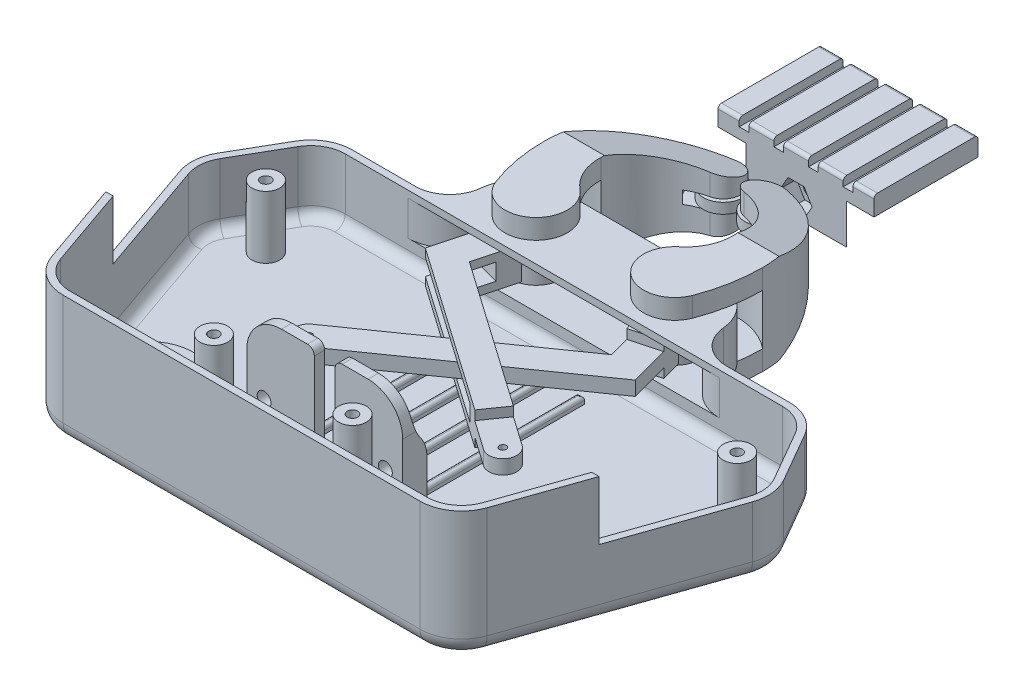
SolidWorks part; units mm, degrees
ref_plane "Front Plane" through (0, 0, 0) normal (0, 0, 1) x (1, 0, 0)
ref_plane "Top Plane" through (0, 0, 0) normal (0, 1, 0) x (1, 0, 0)
ref_plane "Right Plane" through (0, 0, 0) normal (1, 0, 0) x (0, 0, -1)
sketch "Sketch1" plane through (0, 0, 0) normal (0, 1, 0) x (1, 0, 0)
  line L0 (-70, -55) -> (-35, -55)
  line L1 (70, -55) -> (84.4338, -80)
  line L2 (84.4338, -80) -> (60, -150)
  line L3 (60, -150) -> (-60, -150)
  line L4 (-60, -150) -> (-84.4338, -80)
  line L5 (-84.4338, -80) -> (-70, -55)
  line L6 (-35, -55) -> (-35, -35)
  line L7 (-35, -35) -> (35, -35)
  line L8 (35, -35) -> (35, -55)
  line L9 (0, -55) -> (0, -122.8119) construction
  line L10 (35, -55) -> (70, -55)
  point P15 (0, -150)
  dimension "D1" = 25
  dimension "D2" = 140
  dimension "D3" = 70
  dimension "D4" = 120
  dimension "D5" = 70
  dimension "D6" = 55
  dimension "D7" = 120
  dimension "D8" = 20
  dimension "D9" = 70
  dimension "D10" = 35
extrude "Boss-Extrude1" add sketch "Sketch1" along normal blind 2
sketch "Sketch2" plane through (0, 2, 0) normal (0, 1, 0) x (1, 0, 0)
  line L0 (84.4338, -80) -> (70, -55) construction
  line L1 (60, -150) -> (84.4338, -80) construction
  line L2 (-60, -150) -> (60, -150) construction
  line L3 (-84.4338, -80) -> (-60, -150) construction
  line L4 (-70, -55) -> (-84.4338, -80) construction
  line L6 (84.4338, -80) -> (70, -55)
  line L7 (60, -150) -> (84.4338, -80)
  line L8 (-60, -150) -> (60, -150)
  line L9 (-84.4338, -80) -> (-60, -150)
  line L10 (-70, -55) -> (-84.4338, -80)
  line L11 (70, -55) -> (35, -55)
  line L12 (68.8453, -57) -> (33, -57)
  line L13 (-68.8453, -57) -> (-82.2434, -80.2062)
  line L14 (-82.2434, -80.2062) -> (-58.5798, -148)
  line L15 (-58.5798, -148) -> (58.5798, -148)
  line L16 (58.5798, -148) -> (82.2434, -80.2062)
  line L17 (82.2434, -80.2062) -> (68.8453, -57)
  line L18 (-35, -55) -> (-35, -35)
  line L19 (-35, -35) -> (35, -35)
  line L20 (35, -35) -> (35, -55)
  line L21 (-35, -55) -> (-70, -55)
  line L22 (-33, -57) -> (-33, -37)
  line L23 (70, -55) -> (-70, -55) construction
  line L24 (-33, -37) -> (33, -37)
  line L25 (33, -37) -> (33, -57)
  line L26 (-33, -57) -> (-68.8453, -57)
  line L28 (68.8453, -57) -> (-68.8453, -57) construction
  dimension "D1" = 2
  dimension "D2" = 2
  dimension "D3" = 2
  dimension "D4" = 2
extrude "Boss-Extrude2" add sketch "Sketch2" along normal blind 35
sketch "Sketch20" plane through (0, 0, 0) normal (0, -1, 0) x (1, 0, 0)
  line L0 (70, 55) -> (35, 55) construction
  line L1 (-35, 35) -> (35, 35)
  line L2 (-35, 35) -> (-35, 55)
  line L3 (-35, 55) -> (35, 55)
  line L4 (35, 35) -> (35, 55)
  line L5 (35, 55) -> (35, 35) construction
  line L6 (35, 35) -> (-35, 35) construction
  line L7 (-35, 35) -> (-35, 55) construction
extrude "Cut-Extrude7" cut sketch "Sketch20" against normal blind 8
sketch "Sketch21" plane through (0, 8, 0) normal (0, -1, 0) x (1, 0, 0)
  line L1 (-35, 35) -> (35, 35)
  line L2 (-35, 35) -> (-35, 55)
  line L3 (-35, 55) -> (35, 55)
  line L4 (35, 35) -> (35, 55)
extrude "Boss-Extrude12" add sketch "Sketch21" along normal blind 2
sketch "Sketch22" plane through (0, 0, 55) normal (0, 0, 1) x (1, 0, 0)
  line L1 (-33, 2) -> (33, 2)
  line L2 (-33, 2) -> (-33, 8)
  line L3 (-33, 8) -> (33, 8)
  line L4 (33, 2) -> (33, 8)
extrude "Boss-Extrude13" add sketch "Sketch22" along normal blind 2
sketch "Sketch23" plane through (0, 37, 0) normal (0, 1, 0) x (1, 0, 0)
  line L0 (35, -35) -> (-35, -35) construction
  line L1 (-35, -57) -> (35, -57)
  line L2 (-35, -57) -> (-35, -35)
  line L3 (-35, -35) -> (35, -35)
  line L4 (35, -57) -> (35, -35)
  line L5 (-35, -35) -> (-35, -55) construction
  line L6 (35, -55) -> (35, -35) construction
  line L7 (33, -57) -> (-33, -57) construction
extrude "Cut-Extrude8" cut sketch "Sketch23" against normal offset from surface (19 mm away) 12 up to face at (0, 6, 45)
sketch "Sketch24" plane through (0, 18, 0) normal (0, 1, 0) x (1, 0, 0)
  line L1 (-35, -35) -> (35, -35)
  line L2 (-35, -35) -> (-35, -57)
  line L3 (-35, -57) -> (35, -57)
  line L4 (35, -35) -> (35, -57)
  line L5 (-35, -35) -> (35, -35) construction
  line L6 (-35, -55) -> (-35, -35) construction
  line L8 (35, -35) -> (35, -55) construction
  line L9 (-35, -57) -> (-68.8453, -57) construction
extrude "Boss-Extrude16" add sketch "Sketch24" along normal blind 2
sketch "Sketch26" plane through (0, 0, 0) normal (0, -1, 0) x (1, 0, 0)
  line L0 (0, 35) -> (0, 168.1743) construction
  line L1 (-35, 35) -> (35, 35) construction
  circle A0 centre (20, 45) radius 7.5
  circle A1 centre (-20, 45) radius 7.5
  dimension "D1" = 15
  dimension "D2" = 10
  dimension "D3" = 20
extrude "Cut-Extrude9" cut sketch "Sketch26" against normal through all
sketch "Sketch27" plane through (0, 8, 0) normal (0, 1, 0) x (1, 0, 0)
  line L0 (-29.5, -45) -> (-27.5, -45)
  line L1 (-10.5, -45) -> (-12.5, -45)
  line L2 (0, -35) -> (0, -72.4721) construction
  line L3 (35, -35) -> (-35, -35) construction
  line L4 (29.5, -45) -> (27.5, -45)
  line L5 (10.5, -45) -> (12.5, -45)
  arc A0 (-27.5, -45) -> (-12.5, -45) centre (-20, -45) cw
  circle A1 centre (-20, -45) radius 7.5 construction
  arc A2 (-10.5, -45) -> (-29.5, -45) centre (-20, -45) ccw
  arc A3 (27.5, -45) -> (12.5, -45) centre (20, -45) ccw
  arc A4 (10.5, -45) -> (29.5, -45) centre (20, -45) cw
  dimension "D1" = 9.5
extrude "Boss-Extrude18" add sketch "Sketch27" along normal up to surface (10 mm away) up to face at (20, 18, 52.5)
sketch "Sketch25" plane through (0, 20, 0) normal (0, 1, 0) x (1, 0, 0)
  line L0 (35, -57) -> (35, -55) construction
  line L1 (-35, -57) -> (35, -57)
  line L2 (-35, -57) -> (-35, -55)
  line L3 (-35, -55) -> (35, -55)
  line L4 (35, -57) -> (35, -55)
  line L5 (-35, -57) -> (35, -57) construction
  line L6 (-35, -55) -> (-35, -57) construction
  line L7 (-35, -55) -> (-70, -55) construction
extrude "Boss-Extrude17" add sketch "Sketch25" along normal up to surface (17 mm away) up to face at (0, 37, 85.2758)
fillet "Fillet8" radius 10 2 edges at (-33, 13, 37) (33, 13, 37)
fillet "Fillet9" radius 12 2 edges at (35, 13, 35) (-35, 13, 35)
sketch "Sketch32" plane through (0, 6, 0) normal (0, -1, 0) x (1, 0, 0)
  circle A0 centre (-20, 45) radius 7.35
  circle A1 centre (-20, 45) radius 7.5 construction
  dimension "D1" = 14.7
extrude "Boss-Extrude22" add sketch "Sketch32" against normal offset from surface (14.6 mm away) 0.3 from offset 0.3 separate body up to face at (0, 20, 44.8382) offset beyond the face yes
ref_plane "Plane6" through (0, 13, 0) normal (0, -1, 0) x (-1, 0, 0)
sketch "Sketch34" plane through (0, 13, 0) normal (0, -1, 0) x (-1, 0, 0)
  line L0 (0, -55) -> (0, -6.1056) construction
  line L1 (-35, -55) -> (35, -55) construction
  circle A0 centre (6, -5) radius 6
  circle A1 centre (20, -45) radius 7.5 construction
  circle A2 centre (20, -45) radius 7.5 construction
  circle A3 centre (6, -5) radius 2.8
  dimension "D1" = 12
  dimension "D3" = 5.6
  dimension "D2" = 40
extrude "Boss-Extrude23" add sketch "Sketch34" along normal mid plane 3 separate body
sketch "Sketch36" plane through (0, 13, 0) normal (0, -1, 0) x (-1, 0, 0)
  circle A0 centre (6, -5) radius 2.5
  dimension "D1" = 5
extrude "Boss-Extrude24" add sketch "Sketch36" along normal mid plane 3.6 separate body
sketch "Sketch37" plane through (0, 11.2, 0) normal (0, -1, 0) x (1, 0, 0)
  line L0 (-1.0405, 27.7489) -> (-20, 45) construction
  line L1 (-6, 5) -> (-1.0405, 27.7489) construction
  line L2 (0.4875, 31.2396) -> (-20, 45) construction
  line L3 (0.4875, 31.2396) -> (-6, 5) construction
  arc A0 (-4.935, 9.8853) -> (-7.2001, 0.1462) centre (-6, 5) cw
  circle A1 centre (-20, 45) radius 7.35 construction
  arc A2 (-14.5636, 40.0535) -> (-26.1015, 49.0981) centre (-20, 45) ccw construction
  arc A3 (-4.935, 9.8853) -> (-14.5636, 40.0535) centre (-1.0405, 27.7489) cw construction
  arc A4 (-26.1015, 49.0981) -> (-7.2001, 0.1462) centre (0.4875, 31.2396) ccw construction
  arc A5 (-31.5421, 31.1877) -> (-19.3089, 27.0133) centre (-20, 45) ccw
  arc A6 (-31.5421, 31.1877) -> (-7.2001, 0.1462) centre (0.4875, 31.2396) ccw
  arc A7 (-19.3089, 27.0133) -> (-4.935, 9.8853) centre (-1.0405, 27.7489) ccw
  dimension "D1" = 5
  dimension "D4" = 18
  dimension "D2" = 60
  dimension "D3" = 70
extrude "Boss-Extrude25" add sketch "Sketch37" along normal up to surface (11.2 mm away) up to face at (0, 0, 95)
sketch "Sketch39" plane through (0, 5.7, 0) normal (0, -1, 0) x (1, 0, 0)
  arc A0 (-14.3353, 38.0064) -> (-28.4038, 48.2211) centre (-20, 45) ccw
  arc A1 (-31.5421, 31.1877) -> (-19.3089, 27.0133) centre (-20, 45) ccw construction
  arc A2 (-31.5421, 31.1877) -> (-19.3089, 27.0133) centre (-20, 45) ccw
  arc A3 (-31.5421, 31.1877) -> (-28.4038, 48.2211) centre (15.8356, 31.2644) cw
  arc A4 (-31.5421, 31.1877) -> (-7.2001, 0.1462) centre (0.4875, 31.2396) ccw construction
  arc A5 (-19.3089, 27.0133) -> (-14.3353, 38.0064) centre (-5.8694, 27.5545) cw
  arc A6 (-19.3089, 27.0133) -> (-4.935, 9.8853) centre (-1.0405, 27.7489) ccw construction
  dimension "D1" = 18
extrude "Boss-Extrude26" add sketch "Sketch39" along direction (0, -1, 0) on the side of the normal up to surface (5.7 mm away) up to face at (-16.6764, 0, 14.8256)
sketch "Sketch40" plane through (0, 20.3, 0) normal (0, 1, 0) x (1, 0, 0)
  arc A1 (-28.4038, -48.2211) -> (-14.3353, -38.0064) centre (-20, -45) ccw construction
  arc A2 (-19.3089, -27.0133) -> (-14.3353, -38.0064) centre (-5.8694, -27.5545) ccw construction
  arc A3 (-19.3089, -27.0133) -> (-31.5421, -31.1877) centre (-20, -45) ccw construction
  arc A4 (-31.5421, -31.1877) -> (-28.4038, -48.2211) centre (15.8356, -31.2644) ccw construction
  arc A5 (-28.4038, -48.2211) -> (-14.3353, -38.0064) centre (-20, -45) ccw
  arc A6 (-19.3089, -27.0133) -> (-14.3353, -38.0064) centre (-5.8694, -27.5545) ccw
  arc A7 (-19.3089, -27.0133) -> (-31.5421, -31.1877) centre (-20, -45) ccw
  arc A8 (-31.5421, -31.1877) -> (-28.4038, -48.2211) centre (15.8356, -31.2644) ccw
extrude "Boss-Extrude27" add sketch "Sketch40" along normal blind 5.7
sketch "Sketch41" plane through (0, 14.8, 0) normal (0, 1, 0) x (1, 0, 0)
  arc A0 (-4.935, -9.8853) -> (-7.2001, -0.1462) centre (-6, -5) ccw construction
  arc A1 (-19.3089, -27.0133) -> (-31.5421, -31.1877) centre (-20, -45) ccw construction
  arc A2 (-4.935, -9.8853) -> (-19.3089, -27.0133) centre (-1.0405, -27.7489) ccw construction
  arc A3 (-7.2001, -0.1462) -> (-31.5421, -31.1877) centre (0.4875, -31.2396) ccw construction
  arc A4 (-4.935, -9.8853) -> (-7.2001, -0.1462) centre (-6, -5) ccw
  arc A5 (-19.3089, -27.0133) -> (-31.5421, -31.1877) centre (-20, -45) ccw
  arc A6 (-4.935, -9.8853) -> (-19.3089, -27.0133) centre (-1.0405, -27.7489) ccw
  arc A7 (-7.2001, -0.1462) -> (-31.5421, -31.1877) centre (0.4875, -31.2396) ccw
extrude "Boss-Extrude28" add sketch "Sketch41" along normal up to surface (11.2 mm away) up to face at (-22.3518, 26, 38.2988)
sketch "Sketch43" plane through (0, 11.2, 0) normal (0, 1, 0) x (1, 0, 0)
  arc A1 (-4.935, -9.8853) -> (-19.3089, -27.0133) centre (-1.0405, -27.7489) ccw construction
  arc A3 (-19.3089, -27.0133) -> (-31.5421, -31.1877) centre (-20, -45) ccw construction
  arc A5 (-10.5871, -12.156) -> (-19.3089, -27.0133) centre (-1.0405, -27.7489) ccw
  arc A6 (-7.2001, -0.1462) -> (-31.5421, -31.1877) centre (0.4875, -31.2396) ccw construction
  arc A7 (-19.3089, -27.0133) -> (-31.5421, -31.1877) centre (-20, -45) ccw
  arc A8 (-14.2045, -2.7783) -> (-10.5871, -12.156) centre (-6, -5) ccw
  arc A9 (-14.2045, -2.7783) -> (-31.5421, -31.1877) centre (0.4875, -31.2396) ccw
  arc A13 (-4.935, -9.8853) -> (-7.2001, -0.1462) centre (-6, -5) ccw construction
  dimension "D1" = 17
extrude "Boss-Extrude29" add sketch "Sketch43" along normal up to surface (3.6 mm away) up to face at (-6, 14.8, 2.5)
sketch "Sketch44" plane through (0, 0, 0) normal (1, 0, 0) x (0, 0, -1)
  line L0 (0, 17.8) -> (-26.0133, 26)
  line L1 (-26.0133, 26) -> (0, 26)
  line L4 (0, 14.8) -> (0, 26) construction
  line L5 (-9.8853, 26) -> (-27.0133, 26) construction
  line L6 (0, 17.8) -> (0, 26)
  line L7 (-15.422, 13) -> (22.0298, 13) construction
  line L8 (-94.4278, 13) -> (94.4278, 13) construction
  line L9 (0, 8.2) -> (-26.0133, 0)
  line L10 (-26.0133, 0) -> (0, 0)
  line L11 (0, 8.2) -> (0, 0)
  dimension "D1" = 1
  dimension "D2" = 3
extrude "Cut-Extrude10" cut sketch "Sketch44" against normal up to surface (31.1129 mm away) up to face at (-19.4224, 13, 12.2098)
ref_plane "Plane2" through (0, 0, 0) normal (1, 0, 0) x (0, 0, -1)
ref_plane "Plane3" through (0, 0, 126) normal (0, 0, -1) x (-1, 0, 0)
sketch "Sketch45" plane through (0, 13, 0) normal (0, -1, 0) x (-1, 0, 0)
  circle A0 centre (6, -5) radius 6 construction
  circle A1 centre (6, -5) radius 6
  circle A2 centre (6, -5) radius 5.75
  dimension "D1" = 11.5
extrude "Cut-Extrude11" cut sketch "Sketch45" along normal up to surface (1.5 mm away) from surface up to face at (-6, 11.5, -1) starting at face at (-6, 14.5, -1)
mirror "Mirror8" about plane through (0, 0, 0) normal (1, 0, 0) of bodies 137 140
sketch "Sketch8" plane through (0, 0, 126) normal (0, 0, -1) x (-1, 0, 0)
  line L0 (-68.8453, 2) -> (68.8453, 2) construction
  line L1 (-68.8453, 2) -> (68.8453, 2) construction
  line L2 (60, 0) -> (-60, 0) construction
  line L3 (22.5, 2) -> (-22.5, 2)
  line L4 (22.5, 2) -> (22.5, 36)
  line L5 (22.5, 36) -> (-22.5, 36)
  line L6 (-22.5, 2) -> (-22.5, 36)
  line L7 (60, 0) -> (-60, 0) construction
  line L8 (0, 14.8493) -> (0, -14.8493) construction
  dimension "D1" = 34
  dimension "D2" = 45
  dimension "D3" = 22.5
extrude "Boss-Extrude5" add sketch "Sketch8" along normal blind 3
sketch "Sketch9" plane through (0, 2, 0) normal (0, 1, 0) x (1, 0, 0)
  line L1 (-22.5, -123) -> (-19.5, -123)
  line L2 (-22.5, -123) -> (-22.5, -119)
  line L3 (-22.5, -119) -> (-19.5, -119)
  line L4 (-19.5, -123) -> (-19.5, -119)
  line L5 (22.5, -123) -> (19.5, -123)
  line L6 (22.5, -123) -> (22.5, -119)
  line L7 (22.5, -119) -> (19.5, -119)
  line L8 (19.5, -123) -> (19.5, -119)
  dimension "D1" = 3
  dimension "D2" = 4
extrude "Boss-Extrude6" add sketch "Sketch9" along normal blind 20
fillet "Fillet1" radius 10 2 edges at (-21, 22, 123) (21, 22, 123)
fillet "Fillet2" radius 10 2 edges at (-21, 22, 119) (21, 22, 119)
sketch "Sketch11" plane through (0, 2, 0) normal (0, 1, 0) x (1, 0, 0)
  line L0 (-58.5798, -148) -> (58.5798, -148) construction
  circle A0 centre (-43.5798, -133) radius 12.5
  dimension "D1" = 25
  dimension "D2" = 15
  dimension "D3" = 15
extrude "Boss-Extrude9" add sketch "Sketch11" along normal blind 10
ref_plane "Plane4" through (0, 7, 0) normal (0, 1, 0) x (1, 0, 0)
sketch "Sketch13" plane through (0, 7, 0) normal (0, 1, 0) x (1, 0, 0)
  line L0 (-53.0211, -136.2955) -> (-58.294, -121.1894)
  line L1 (-82.2434, -80.2062) -> (-58.5798, -148) construction
  line L2 (-34.1384, -129.7045) -> (-39.4113, -114.5983)
  line L3 (-58.294, -121.1894) -> (-39.4113, -114.5983)
  arc A0 (-53.0211, -136.2955) -> (-34.1384, -129.7045) centre (-43.5798, -133) ccw
  dimension "D1" = 20
  dimension "D2" = 16
extrude "Cut-Extrude3" cut sketch "Sketch13" along normal blind 5 from offset 3 offset against normal yes
sketch "Sketch14" plane through (0, 12, 0) normal (0, 1, 0) x (1, 0, 0)
  circle A0 centre (-43.5798, -133) radius 2.5
  circle A1 centre (-43.5798, -133) radius 12.5 construction
  dimension "D1" = 5
extrude "Cut-Extrude4" cut sketch "Sketch14" against normal up to surface (8 mm away) up to face at (-44.4037, 4, 130.6397)
sketch "Sketch15" plane through (0, 0, 126) normal (0, 0, 1) x (1, 0, 0)
  line L1 (22.5, 2) -> (-22.5, 2) construction
  line L2 (22.5, 2) -> (-22.5, 2) construction
  line L3 (0, -14.8493) -> (0, 14.8493) construction
  circle A0 centre (17.5, 16) radius 2
  circle A1 centre (-17.5, 16) radius 2
  circle A3 centre (0, 8) radius 4.65
  dimension "D1" = 8
  dimension "D2" = 4
  dimension "D3" = 4
  dimension "D6" = 9.3
  dimension "D4" = 35
  dimension "D5" = 17.5
  dimension "D7" = 6
extrude "Cut-Extrude5" cut sketch "Sketch15" against normal up to surface (3 mm away) up to face at (0, 24.5, 123)
fillet "Fillet3" radius 10 8 edges at (-35, 13, 55) (35, 13, 55) (58.5798, 19.5, 148) (-58.5798, 19.5, 148) (82.2434, 19.5, 80.2062) (68.8453, 19.5, 57) (-82.2434, 19.5, 80.2062) (-68.8453, 19.5, 57)
fillet "Fillet4" radius 12 8 edges at (-60, 18.5, 150) (-84.4338, 18.5, 80) (-70, 18.5, 55) (-33, 13, 57) (33, 13, 57) (70, 18.5, 55) (60, 18.5, 150) (84.4338, 18.5, 80)
fillet "Fillet5" radius 10 2 edges at (22.5, 36, 124.5) (-22.5, 36, 124.5)
fillet "Fillet6" radius 3 12 edges at (-70.8266, 2, 112.9143) (-81.2478, 2, 80.3) (-75.842, 2, 69.1187) (-68.0718, 2, 58.3397) (0, 2, 57) (68.0718, 2, 58.3397) (75.842, 2, 69.1187) (81.2478, 2, 80.3) (70.8266, 2, 112.9143) (0, 2, 148) (-57.2685, 2, 146.1534) (57.2685, 2, 146.1534)
fillet "Fillet7" radius 5 12 edges at (69.0718, 0, 56.6077) (77.5741, 0, 68.1187) (83.2389, 0, 80.1125) (72.7148, 0, 113.5734) (58.4264, 0, 147.7841) (0, 0, 150) (-58.4264, 0, 147.7841) (-72.7148, 0, 113.5734) (-83.2389, 0, 80.1125) (-77.5741, 0, 68.1187) (-69.0718, 0, 56.6077) (0, 0, 55)
sketch "Sketch16" plane through (0, 0, 0) normal (1, 0, 0) x (0, 0, -1)
  line L0 (-83.5443, 0) -> (-140.3069, 0) construction
  line L1 (-118, 40) -> (-28, 40)
  line L2 (-118, 40) -> (-118, 20)
  line L3 (-118, 20) -> (-28, 20)
  line L4 (-28, 40) -> (-28, 20)
  line L5 (-150, 5) -> (-150, 37) construction
  dimension "D1" = 20
  dimension "D2" = 32
  dimension "D3" = 20
  dimension "D4" = 90
extrude "Cut-Extrude6" cut sketch "Sketch16" against normal through all both and the other way through all
sketch "Sketch17" plane through (0, 2, 0) normal (0, 1, 0) x (1, 0, 0)
  line L0 (0, -14.8493) -> (0, 14.8493) construction
  line L4 (-63.0718, -55) -> (-44.9089, -55) construction
  circle A2 centre (-68, -75) radius 4
  circle A4 centre (-68, -75) radius 1.5
  circle A10 centre (68, -75) radius 1.5
  circle A11 centre (68, -75) radius 4
  dimension "D7" = 8
  dimension "D9" = 3
  dimension "D4" = 20
  dimension "D5" = 68
extrude "Boss-Extrude10" add sketch "Sketch17" along normal up to surface (18 mm away) up to face at (0, 20, 71.1525)
sketch "Sketch19" plane through (0, 2, 0) normal (0, 1, 0) x (1, 0, 0)
  line L0 (0, -14.8493) -> (0, 14.8493) construction
  line L1 (-51.4786, -150) -> (51.4786, -150) construction
  circle A0 centre (-20, -138) radius 4
  circle A1 centre (-20, -138) radius 1.5
  circle A2 centre (20, -138) radius 1.5
  circle A3 centre (20, -138) radius 4
  dimension "D1" = 3
  dimension "D2" = 8
  dimension "D3" = 20
  dimension "D4" = 12
extrude "Boss-Extrude11" add sketch "Sketch19" along normal up to surface (35 mm away) up to face at (0, 37, 136.7604)
sketch "Sketch46" plane through (0, 0, 126) normal (0, 0, 1) x (1, 0, 0)
  line L0 (-3, 8) -> (-3, 36)
  line L1 (-3, 36) -> (3, 36)
  line L3 (-3, 8) -> (3, 8)
  line L5 (-12.5, 36) -> (12.5, 36) construction
  line L7 (3, 36) -> (3, 8)
  circle A0 centre (0, 8) radius 4.65 construction
  circle A1 centre (0, 8) radius 4.65 construction
  dimension "D1" = 6
extrude "Cut-Extrude12" cut sketch "Sketch46" against normal up to surface (3 mm away) up to face at (-4.65, 8, 123)
fillet "Fillet10" radius 2 2 edges at (-3, 36, 124.5) (3, 36, 124.5)
mirror "Mirror9" about plane through (0, 0, 0) normal (1, 0, 0) of "Cut-Extrude4", "Cut-Extrude3", "Boss-Extrude9"
sketch "Sketch49" plane through (0, 13, 0) normal (0, -1, 0) x (-1, 0, 0)
  line L0 (20, -45) -> (6, -5) construction
  line L1 (27.0996, -43.0977) -> (32.923, -64.831) construction
  line L2 (30.3078, -66.6622) -> (-25.7197, -105.8931)
  line L3 (12.9004, -46.9023) -> (17.9052, -65.5804) construction
  line L4 (17.9052, -65.5804) -> (-30.3083, -99.3398)
  line L5 (63.0718, -57) -> (-63.0718, -57) construction
  line L6 (30.3078, -66.6622) -> (25.7352, -49.5968)
  line L7 (20.5204, -63.7492) -> (17.3316, -51.8485)
  line L8 (17.9052, -65.5804) -> (20.5204, -63.7492)
  line L9 (30.3078, -66.6622) -> (32.923, -64.831) construction
  circle A0 centre (20, -45) radius 7.35 construction
  arc A1 (17.3316, -51.8485) -> (25.7352, -49.5968) centre (20, -45) ccw
  circle A2 centre (20, -45) radius 75 construction
  arc A3 (7.2001, -0.1462) -> (4.935, -9.8853) centre (6, -5) ccw construction
  arc A4 (7.2001, -0.1462) -> (4.935, -9.8853) centre (6, -5) ccw construction
  arc A5 (-30.3083, -99.3398) -> (-25.7197, -105.8931) centre (-28.014, -102.6165) ccw
  point P15 (26.4546, -40.6906)
  point P19 (0, 0)
  point P20 (27.0996, -43.0977)
  dimension "D1" = 150
  dimension "D2" = 110
  dimension "D3" = 4
  dimension "D4" = 22.5
  dimension "D5" = 35
  dimension "D6" = 3
  dimension "D7" = 3
extrude "Boss-Extrude30" add sketch "Sketch49" along normal offset from surface 0.3 and the other way offset from surface 0.3 separate body up to face at (0, 8, 45.5486) other way up to face at (0, 18, 45.5486)
sketch "Sketch50" plane through (-41.2919, 0, 58.971) normal (-0.5736, 0, 0.8192) x (0.8192, 0, 0.5736)
  line L0 (13.4091, 8.3) -> (13.4091, 17.7) construction
  line L1 (13.4091, 15.4) -> (65.8061, 15.4)
  line L2 (13.4091, 15.4) -> (13.4091, 10.6)
  line L3 (13.4091, 10.6) -> (65.8061, 10.6)
  line L4 (65.8061, 15.4) -> (65.8061, 10.6)
  line L5 (85.8061, 8.3) -> (85.8061, 17.7) construction
  line L6 (13.4091, 15.4) -> (13.4091, 17.7) construction
  line L7 (81.8061, 17.7) -> (13.4091, 17.7) construction
  line L8 (13.4091, 10.6) -> (13.4091, 8.3) construction
  line L9 (13.4091, 8.3) -> (81.8061, 8.3) construction
  dimension "D1" = 4.8
  dimension "D2" = 0
  dimension "D3" = 20
extrude "Cut-Extrude13" cut sketch "Sketch50" against normal up to surface (8 mm away) up to face at (4.894, 13, 81.5445)
sketch "Sketch51" plane through (0, 13, 0) normal (0, -1, 0) x (-1, 0, 0)
  line L0 (30.3078, -66.6622) -> (25.7352, -49.5968) construction
  line L1 (17.3316, -51.8485) -> (20.5204, -63.7492) construction
  line L3 (-25.7197, -105.8931) -> (30.3078, -66.6622) construction
  line L6 (20.5204, -63.7492) -> (-30.3083, -99.3398) construction
  line L22 (17.3316, -51.8485) -> (20.5204, -63.7492) construction
  line L23 (20.5204, -63.7492) -> (-30.3083, -99.3398) construction
  line L24 (-25.7197, -105.8931) -> (30.3078, -66.6622) construction
  line L25 (30.3078, -66.6622) -> (25.7352, -49.5968) construction
  line L26 (0, 14.8493) -> (0, -14.8493) construction
  line L27 (-20.5204, -63.7492) -> (30.3083, -99.3398)
  line L28 (-17.3316, -51.8485) -> (-20.5204, -63.7492)
  line L29 (-30.3078, -66.6622) -> (-25.7352, -49.5968)
  line L30 (25.7197, -105.8931) -> (-30.3078, -66.6622)
  arc A0 (17.3316, -51.8485) -> (25.7352, -49.5968) centre (20, -45) ccw construction
  arc A6 (-30.3083, -99.3398) -> (-25.7197, -105.8931) centre (-28.014, -102.6165) ccw construction
  arc A10 (-30.3083, -99.3398) -> (-25.7197, -105.8931) centre (-28.014, -102.6165) ccw construction
  arc A11 (17.3316, -51.8485) -> (25.7352, -49.5968) centre (20, -45) ccw construction
  arc A12 (30.3083, -99.3398) -> (25.7197, -105.8931) centre (28.014, -102.6165) cw
  arc A13 (-17.3316, -51.8485) -> (-25.7352, -49.5968) centre (-20, -45) cw
extrude "Boss-Extrude32" add sketch "Sketch51" along normal offset from surface 0.3 and the other way offset from surface 0.4 up to face at (-9.3465, 10.6, 75.4798) other way up to face at (-9.3465, 15.4, 75.4798)
sketch "Sketch52" plane through (0, 13, 0) normal (0, -1, 0) x (-1, 0, 0)
  line L2 (-25.7352, -49.5968) -> (-30.3078, -66.6622) construction
  line L3 (-20.5204, -63.7492) -> (-17.3316, -51.8485) construction
  line L6 (-25.7352, -49.5968) -> (-27.3076, -55.4652)
  line L7 (-18.9041, -57.717) -> (-17.3316, -51.8485)
  line L9 (-18.9041, -57.717) -> (-27.3076, -55.4652)
  line L10 (63.0718, -57) -> (-63.0718, -57) construction
  arc A0 (-25.7352, -49.5968) -> (-17.3316, -51.8485) centre (-20, -45) ccw construction
  arc A1 (-25.7352, -49.5968) -> (-17.3316, -51.8485) centre (-20, -45) ccw
  circle A2 centre (-20, -45) radius 12 construction
  point P2 (-27.4936, -56.1593)
extrude "Boss-Extrude33" add sketch "Sketch52" along normal up to surface (4.7 mm away) from surface up to face at (-5.8265, 8.3, 73.4601) starting at face at (-5.8265, 17.7, 73.4601)
sketch "Sketch53" plane through (0, 17.7, 0) normal (0, 1, 0) x (1, 0, 0)
  line L0 (-20.5204, -63.7492) -> (30.3083, -99.3398) construction
  line L1 (25.7197, -105.8931) -> (-30.3078, -66.6622) construction
  line L2 (21.8792, -93.4377) -> (30.3083, -99.3398)
  line L3 (25.7197, -105.8931) -> (17.2906, -99.9909)
  line L4 (17.2906, -99.9909) -> (21.8792, -93.4377)
  arc A0 (25.7197, -105.8931) -> (30.3083, -99.3398) centre (28.014, -102.6165) ccw construction
  arc A1 (25.7197, -105.8931) -> (30.3083, -99.3398) centre (28.014, -102.6165) ccw
  point P5 (31.2906, -104.9108)
  dimension "D1" = 14
extrude "Cut-Extrude14" cut sketch "Sketch53" against normal up to surface (2.7 mm away) up to face at (6.2892, 15, 75.1868)
sketch "Sketch54" plane through (0, 8.3, 0) normal (0, -1, 0) x (1, 0, 0)
  line L0 (25.7197, 105.8931) -> (17.2906, 99.9909) construction
  line L1 (21.8792, 93.4377) -> (30.3083, 99.3398) construction
  line L2 (17.2906, 99.9909) -> (21.8792, 93.4377) construction
  line L3 (25.7197, 105.8931) -> (17.2906, 99.9909)
  line L4 (21.8792, 93.4377) -> (30.3083, 99.3398)
  line L5 (17.2906, 99.9909) -> (21.8792, 93.4377)
  arc A0 (30.3083, 99.3398) -> (25.7197, 105.8931) centre (28.014, 102.6165) ccw construction
  arc A1 (30.3083, 99.3398) -> (25.7197, 105.8931) centre (28.014, 102.6165) ccw
extrude "Cut-Extrude15" cut sketch "Sketch54" against normal up to surface (2.6 mm away) up to face at (6.2892, 10.9, 75.1868)
sketch "Sketch55" plane through (0, 15, 0) normal (0, 1, 0) x (1, 0, 0)
  arc A0 (-30.3083, -99.3398) -> (-25.7197, -105.8931) centre (-28.014, -102.6165) ccw construction
  arc A1 (25.7197, -105.8931) -> (30.3083, -99.3398) centre (28.014, -102.6165) ccw construction
  arc A2 (-30.3083, -99.3398) -> (-25.7197, -105.8931) centre (-28.014, -102.6165) ccw construction
  arc A3 (25.7197, -105.8931) -> (30.3083, -99.3398) centre (28.014, -102.6165) ccw construction
  circle A4 centre (-28.014, -102.6165) radius 1
  circle A5 centre (28.014, -102.6165) radius 1
  dimension "D1" = 2
  dimension "D2" = 2
extrude "Cut-Extrude16" cut sketch "Sketch55" against normal up to surface (4.1 mm away) up to face at (6.2892, 10.9, 75.1868)
sketch "Sketch56" plane through (0, 2, 0) normal (0, 1, 0) x (1, 0, 0)
  line L0 (0, -14.8493) -> (0, 14.8493) construction
  line L1 (-16, -119) -> (-14, -119)
  line L2 (-16, -119) -> (-16, -67)
  line L3 (-16, -67) -> (-14, -67)
  line L4 (-14, -119) -> (-14, -67)
  line L5 (-6, -119) -> (-4, -119)
  line L6 (-6, -119) -> (-6, -67)
  line L7 (-6, -67) -> (-4, -67)
  line L8 (-4, -119) -> (-4, -67)
  line L9 (-63.0718, -57) -> (63.0718, -57) construction
  point P10 (-7.2699, -121.6995)
  point P11 (0, 0)
  point P12 (0, 0)
  point P16 (0, 0)
  dimension "D1" = 4
  dimension "D2" = 8
  dimension "D3" = 10
  dimension "D4" = 2
extrude "Boss-Extrude34" add sketch "Sketch56" along normal blind 2
fillet "Fillet11" radius 1 8 edges at (-15, 4, 119) (-5, 4, 119) (-5, 4, 67) (-15, 4, 67) (-4, 4, 93) (-6, 4, 93) (-14, 4, 93) (-16, 4, 93)
mirror "Mirror11" about plane through (0, 0, 0) normal (1, 0, 0) of "Fillet11", "Boss-Extrude34"
sketch "Sketch58" plane through (0, 2, 0) normal (0, 1, 0) x (1, 0, 0)
  line L0 (-22.5, -119) -> (-22.5, -126) construction
  line L1 (-22.5, 40) -> (22.5, 40)
  line L2 (-22.5, 40) -> (-22.5, 10)
  line L3 (-22.5, 10) -> (22.5, 10)
  line L4 (22.5, 40) -> (22.5, 10)
  line L5 (22.5, -119) -> (22.5, -126) construction
  line L6 (23, -35) -> (-23, -35) construction
  dimension "D1" = 30
  dimension "D2" = 45
extrude "Boss-Extrude35" add sketch "Sketch58" along normal offset from surface (17 mm away) 1 separate body up to face at (0, 20, 71.1525)
sketch "Sketch60" plane through (0, 19, 0) normal (0, 1, 0) x (1, 0, 0)
  line L0 (-14, -119) -> (-14, -67) construction
  line L1 (-4, -119) -> (-4, -67) construction
  line L2 (6, -67) -> (6, -119) construction
  line L3 (16, -67) -> (16, -119) construction
  line L4 (14, -119) -> (14, -67) construction
  line L5 (4, -119) -> (4, -67) construction
  line L6 (-6, -67) -> (-6, -119) construction
  line L7 (-16, -67) -> (-16, -119) construction
  line L8 (-14, -119) -> (-14, -67) construction
  line L9 (-4, -119) -> (-4, -67) construction
  line L10 (6, -67) -> (6, -119) construction
  line L11 (16, -46.9969) -> (16, -119) construction
  line L12 (14, -119) -> (14, -67) construction
  line L13 (4, -119) -> (4, -67) construction
  line L14 (-6, -67) -> (-6, -119) construction
  line L15 (-16, -67) -> (-16, -119) construction
  line L16 (16, 40) -> (16, 10) construction
  line L17 (22.5, 40) -> (-22.5, 40) construction
  line L18 (14, 10) -> (14, 40) construction
  line L19 (6, 10) -> (6, 40) construction
  line L20 (4, 10) -> (4, 40) construction
  line L21 (-4, 10) -> (-4, 40) construction
  line L22 (-6, 10) -> (-6, 40) construction
  line L23 (-14, 10) -> (-14, 40) construction
  line L24 (-16, 10) -> (-16, 40) construction
  line L27 (-22.5, 10) -> (22.5, 10) construction
  line L28 (-16, 40) -> (-14, 40) construction
  line L29 (-6, 40) -> (-4, 40) construction
  line L30 (4, 40) -> (6, 40) construction
  line L31 (14, 40) -> (16, 40) construction
  line L32 (16, 10) -> (14, 10) construction
  line L33 (6, 10) -> (4, 10) construction
  line L34 (-4, 10) -> (-6, 10) construction
  line L35 (-14, 10) -> (-16, 10) construction
  line L36 (16.4, 40.4) -> (16.4, 9.6)
  line L37 (16.4, 9.6) -> (13.6, 9.6)
  line L38 (13.6, 9.6) -> (13.6, 40.4)
  line L39 (13.6, 40.4) -> (16.4, 40.4)
  line L40 (6.4, 9.6) -> (6.4, 40.4)
  line L41 (3.6, 40.4) -> (6.4, 40.4)
  line L42 (3.6, 9.6) -> (3.6, 40.4)
  line L43 (6.4, 9.6) -> (3.6, 9.6)
  line L44 (-3.6, 9.6) -> (-3.6, 40.4)
  line L45 (-6.4, 40.4) -> (-3.6, 40.4)
  line L46 (-6.4, 9.6) -> (-6.4, 40.4)
  line L47 (-3.6, 9.6) -> (-6.4, 9.6)
  line L48 (-13.6, 9.6) -> (-13.6, 40.4)
  line L49 (-16.4, 40.4) -> (-13.6, 40.4)
  line L50 (-16.4, 9.6) -> (-16.4, 40.4)
  line L51 (-13.6, 9.6) -> (-16.4, 9.6)
  dimension "D1" = 0.4
extrude "Cut-Extrude17" cut sketch "Sketch60" against normal blind 2.4
fillet "Fillet12" radius 1 10 edges at (-19.45, 19, -10) (-10, 19, -10) (0, 19, -10) (10, 19, -10) (19.45, 19, -10) (19.45, 19, -40) (10, 19, -40) (0, 19, -40) (-10, 19, -40) (-19.45, 19, -40)
sketch "Sketch61" plane through (0, 2, 0) normal (0, -1, 0) x (1, 0, 0)
  line L7 (-22.5, -10) -> (-22.5, -40)
  line L8 (-22.5, -40) -> (22.5, -40)
  line L9 (22.5, -40) -> (22.5, -10)
  line L10 (22.5, -10) -> (14.5, -10)
  line L11 (-22.5, -10) -> (22.5, -10) construction
  line L12 (14.5, -10) -> (6, -18)
  line L13 (6, -18) -> (-6, -18)
  line L15 (-6, -18) -> (-14.5, -10)
  line L16 (-14.5, -10) -> (-22.5, -10)
  dimension "D1" = 8
  dimension "D2" = 8
  dimension "D3" = 8
  dimension "D4" = 12
extrude "Cut-Extrude18" cut sketch "Sketch61" against normal offset from surface (11.5 mm away) 5.5 contours L13 L15 L16 L7 L8 L9 L10 L12 up to face at (-19.45, 19, -25)
sketch "Sketch62" plane through (0, 13.5, 0) normal (0, -1, 0) x (1, 0, 0)
  line L0 (6, -18) -> (-6, -18) construction
  line L1 (0, -18) -> (0, -71.4655) construction
  line L5 (-22.5, -40) -> (22.5, -40) construction
  circle A2 centre (0, -35) radius 5
  point P1 (0, 0)
  dimension "D1" = 10
extrude "Boss-Extrude38" add sketch "Sketch62" along normal blind 10
sketch "Sketch63" plane through (0, 0, -10) normal (0, 0, 1) x (1, 0, 0)
  line L0 (0, -14.8493) -> (0, 14.8493) construction
  line L1 (-3.6, 19) -> (3.6, 19) construction
  circle A0 centre (0, 7) radius 2.9
  point P6 (0, 0)
  dimension "D1" = 5.8
  dimension "D2" = 12
extrude "Cut-Extrude19" cut sketch "Sketch63" against normal up to surface (8 mm away) up to face at (0, 7.75, -18)
sketch "Sketch66" plane through (0, 0, -10) normal (0, 0, 1) x (1, 0, 0)
  line L1 (4.6188, 7) -> (2.3094, 11)
  line L2 (2.3094, 11) -> (-2.3094, 11)
  line L3 (-2.3094, 11) -> (-4.6188, 7)
  line L4 (-4.6188, 7) -> (-2.3094, 3)
  line L5 (-2.3094, 3) -> (2.3094, 3)
  line L6 (2.3094, 3) -> (4.6188, 7)
  circle A0 centre (0, 7) radius 4 construction
  dimension "D1" = 8
extrude "Cut-Extrude20" cut sketch "Sketch66" against normal blind 4.8
sketch "Sketch67" plane through (-11.612, 0, -3.1114) normal (-0.9659, 0, -0.2588) x (-0.2588, 0, 0.9659)
  line L1 (72.235, 15.4) -> (60.645, 15.4)
  line L2 (72.235, 15.4) -> (72.235, 10.6)
  line L3 (72.235, 10.6) -> (60.645, 10.6)
  line L4 (60.645, 15.4) -> (60.645, 10.6)
  point P5 (0, 0)
  dimension "D1" = 11.59
extrude "Cut-Extrude21" cut sketch "Sketch67" against normal up to surface (8.7 mm away) up to face at (-19.4575, 13, 59.7823)
sketch "Sketch68" plane through (0, 2, 0) normal (0, 1, 0) x (1, 0, 0)
  line L2 (-7.5, -126) -> (-7.5, -147)
  line L3 (-7.5, -147) -> (7.5, -147)
  line L4 (7.5, -126) -> (7.5, -147)
  line L6 (-7.5, -126) -> (7.5, -126)
  line L7 (22.5, -126) -> (-22.5, -126) construction
  line L8 (0, -14.8493) -> (0, 14.8493) construction
  dimension "D1" = 21
  dimension "D2" = 15
  dimension "D3" = 7.5
extrude "Cut-Extrude22" cut sketch "Sketch68" along normal blind 5 from offset 1 offset against normal yes
